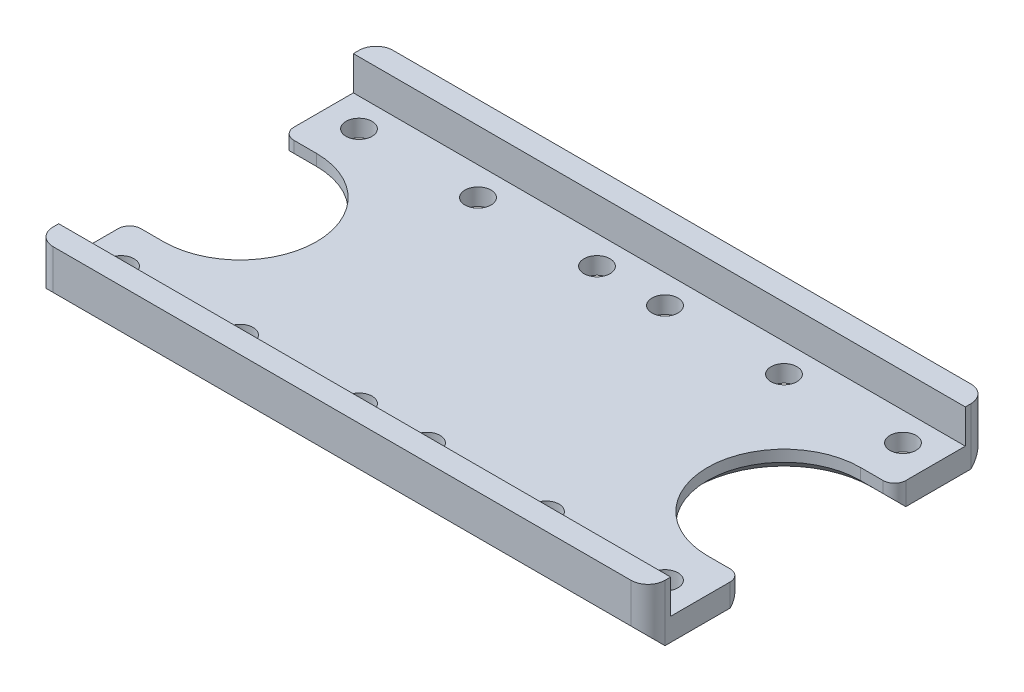
SolidWorks part; units mm, degrees
material "ABS"
ref_plane "正面" through (0, 0, 0) normal (0, 0, 1) x (1, 0, 0)
ref_plane "平面" through (0, 0, 0) normal (0, 1, 0) x (1, 0, 0)
ref_plane "右側面" through (0, 0, 0) normal (1, 0, 0) x (0, 0, -1)
sketch "ｽｹｯﾁ1" plane through (0, 0, 0) normal (1, 0, 0) x (0, 0, -1)
  line L0 (-15, 0) -> (15, 0)
  line L1 (15, 0) -> (15, 5)
  line L2 (15, 5) -> (13, 5)
  line L3 (13, 5) -> (13, 2)
  line L4 (13, 2) -> (-13, 2)
  line L5 (-13, 2) -> (-13, 5)
  line L6 (-13, 5) -> (-15, 5)
  line L7 (-15, 5) -> (-15, 0)
  point P8 (0, 0)
  dimension "D1" = 0
  dimension "D2" = 30
  dimension "D3" = 2
  dimension "D4" = 2
  dimension "D5" = 3
  dimension "D6" = 2
extrude "ﾎﾞｽ - 押し出し1" add sketch "ｽｹｯﾁ1" along normal mid plane 54
sketch "ｽｹｯﾁ2" plane through (0, 2, 0) normal (0, 1, 0) x (1, 0, 0)
  line L0 (24, 6.75) -> (28, 6.75)
  line L1 (28, 6.75) -> (28, -6.75)
  line L2 (28, -6.75) -> (24, -6.75)
  arc A0 (24, 6.75) -> (24, -6.75) centre (24, 0) ccw
  dimension "D1" = 13.5
  dimension "D2" = 24
  dimension "D3" = 0
  dimension "D4" = 4
extrude "ｶｯﾄ - 押し出し1" cut sketch "ｽｹｯﾁ2" against normal up to next
hole_wizard "M2 丸平ねじ用座ぐり穴1" positions "ｽｹｯﾁ3" profile "ｽｹｯﾁ4" counterbore size "M2" standard "JIS" end condition up to next
sketch "ｽｹｯﾁ3" plane through (0, 0, 0) normal (0, -1, 0) x (-1, 0, 0)
  line L0 (-27, -15) -> (27, -15) construction
  arc A0 (-24, -6.75) -> (-24, 6.75) centre (-24, 0) ccw construction
  point P0 (-24, -10.5)
  dimension "D1" = 4.5
  dimension "D2" = 0
sketch "ｽｹｯﾁ4" plane through (24, 0, 10.5) normal (1, 0, 0) x (0, 0, -1)
  line L0 (0, 0) -> (0, 2)
  line L1 (0, 2) -> (1.15, 2)
  line L3 (1.15, 2) -> (1.15, 0.5)
  line L4 (1.15, 0.5) -> (1.9, 0.5)
  line L5 (1.9, 0.5) -> (1.9, 0)
  line L7 (1.9, 0) -> (0, 0)
  line L11 (0, -6.35) -> (0, 107.95) construction
  dimension "通し穴の直径" = 2.3
  dimension "通し穴の深さ" = 2
  dimension "座ぐり穴の直径" = 3.8
  dimension "座ぐり穴の深さ" = 0.5
pattern_linear "直線ﾊﾟﾀｰﾝ1" count 3 spacing 10.5 along (-1, 0, 0) of "M2 丸平ねじ用座ぐり穴1"
mirror "ﾐﾗｰ1" about plane through (0, 0, 0) normal (0, 0, 1) of "直線ﾊﾟﾀｰﾝ1", "M2 丸平ねじ用座ぐり穴1"
chamfer "面取り1" distance 1 angle 45 3 edges at (25.5, 0, 6.75) (25.5, 0, -6.75) (17.25, 0, 0) tangent propagation no
mirror "ﾐﾗｰ3" about plane through (0, 0, 0) normal (1, 0, 0) of "面取り1", "ﾐﾗｰ1", "直線ﾊﾟﾀｰﾝ1", "M2 丸平ねじ用座ぐり穴1", "ｶｯﾄ - 押し出し1"
fillet "ﾌｨﾚｯﾄ1" radius 1.5 4 edges at (27, 2.5, -15) (27, 2.5, 15) (-27, 2.5, -15) (-27, 2.5, 15)
fillet "ﾌｨﾚｯﾄ2" radius 1 4 edges at (27, 1.5, -6.75) (27, 1.5, 6.75) (-27, 1.5, -6.75) (-27, 1.5, 6.75)
chamfer "面取り2" distance 1.5 angle 45 2 edges at (0, 0, -15) (0, 0, 15) tangent propagation no
